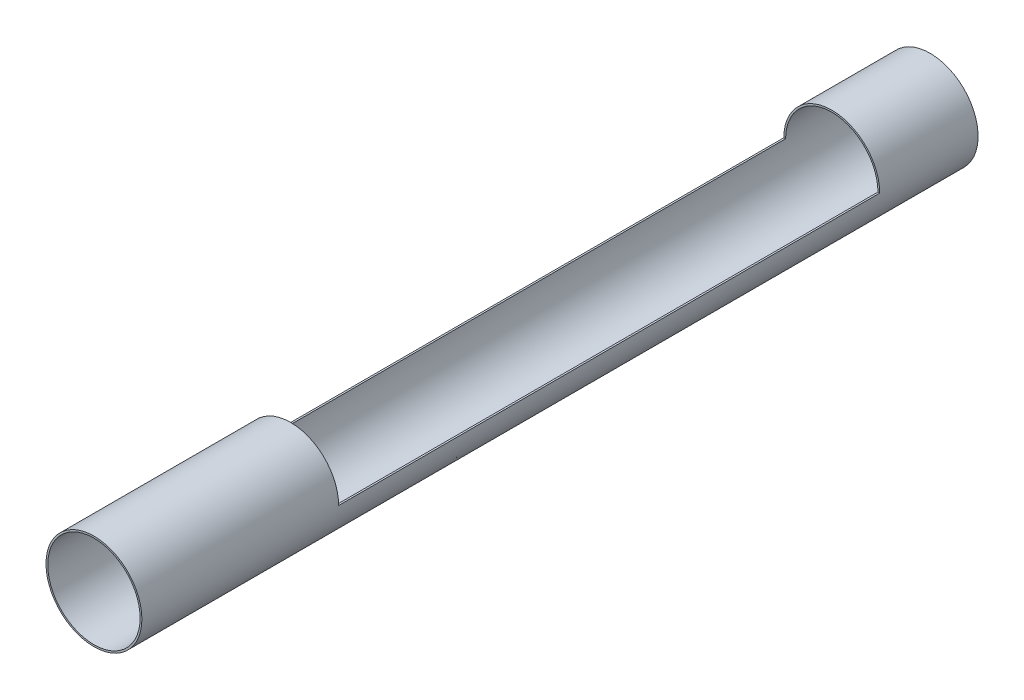
SolidWorks part; units mm, degrees
ref_plane "Front Plane" through (0, 0, 0) normal (0, 0, 1) x (1, 0, 0)
ref_plane "Top Plane" through (0, 0, 0) normal (0, 1, 0) x (1, 0, 0)
ref_plane "Right Plane" through (0, 0, 0) normal (1, 0, 0) x (0, 0, -1)
sketch "Sketch1" plane through (0, 0, 0) normal (0, 0, 1) x (1, 0, 0)
  line L0 (-49.5046, 0) -> (-47.6885, 0)
  line L1 (47.6885, 0) -> (49.5046, 0)
  arc A0 (-49.5046, 0) -> (49.5046, 0) centre (0, 0) ccw
  arc A1 (-47.6885, 0) -> (47.6885, 0) centre (0, 0) ccw
  dimension "D1" = 95.377
  dimension "D2" = 99.0092
extrude "Boss-Extrude1" add sketch "Sketch1" along normal blind 558.8
sketch "Sketch2" plane through (0, 0, 558.8) normal (0, 0, 1) x (1, 0, 0)
  circle A0 centre (0, 0) radius 47.6885
  circle A1 centre (0, 0) radius 49.5046
  arc A2 (-47.6885, 0) -> (47.6885, 0) centre (0, 0) ccw construction
  arc A3 (-49.5046, 0) -> (49.5046, 0) centre (0, 0) ccw construction
extrude "Boss-Extrude2" add sketch "Sketch2" along normal blind 203.2
sketch "Sketch3" plane through (0, 0, 0) normal (0, 0, -1) x (-1, 0, 0)
  circle A0 centre (0, 0) radius 47.6885
  circle A1 centre (0, 0) radius 49.5046
  arc A2 (-47.6885, 0) -> (47.6885, 0) centre (0, 0) ccw construction
  arc A3 (-49.5046, 0) -> (49.5046, 0) centre (0, 0) ccw construction
extrude "Boss-Extrude3" add sketch "Sketch3" along normal blind 101.6
